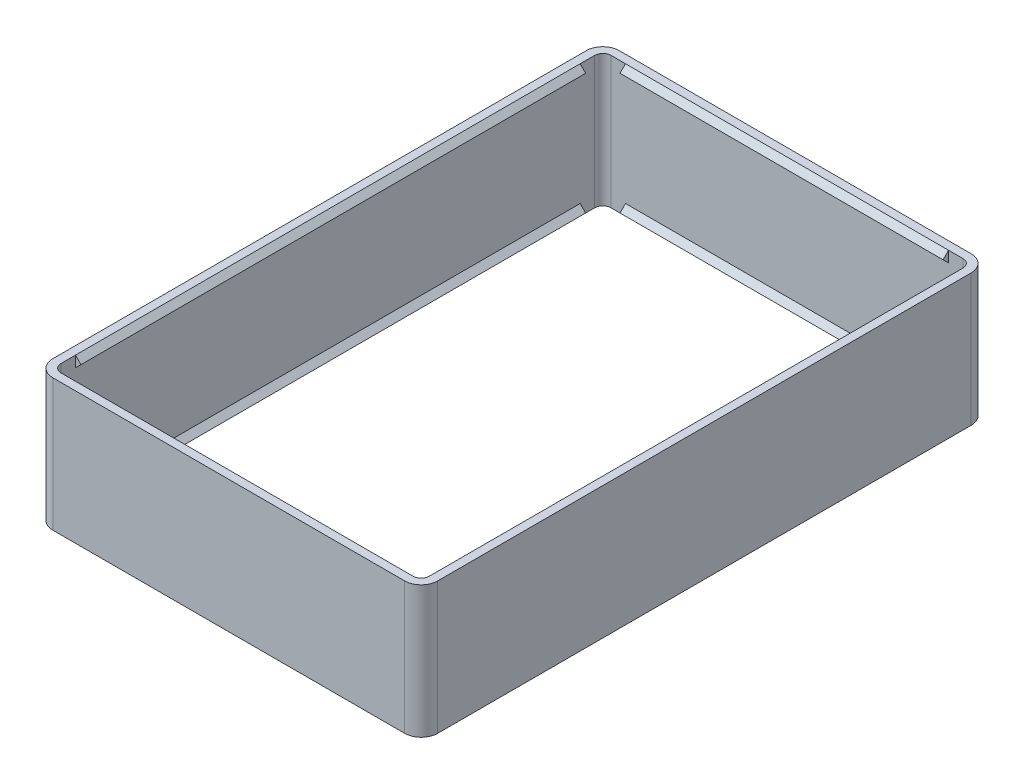
SolidWorks part; units mm, degrees
ref_plane "Front Plane" through (0, 0, 0) normal (0, 0, 1) x (1, 0, 0)
ref_plane "Top Plane" through (0, 0, 0) normal (0, 1, 0) x (1, 0, 0)
ref_plane "Right Plane" through (0, 0, 0) normal (1, 0, 0) x (0, 0, -1)
sketch "Sketch1" plane through (0, 0, 0) normal (0, 1, 0) x (1, 0, 0)
  line L1 (-30.48, -46.99) -> (30.48, -46.99) construction
  line L2 (-30.48, -46.99) -> (-30.48, 46.99) construction
  line L3 (-30.48, 46.99) -> (30.48, 46.99) construction
  line L4 (30.48, -46.99) -> (30.48, 46.99) construction
  line L5 (-30.48, -46.99) -> (30.48, 46.99) construction
  line L6 (-30.48, 46.99) -> (30.48, -46.99) construction
  line L7 (-34.98, -51.49) -> (34.98, -51.49)
  line L8 (-34.98, -51.49) -> (-34.98, 51.49)
  line L9 (-34.98, 51.49) -> (34.98, 51.49)
  line L10 (34.98, -51.49) -> (34.98, 51.49)
  line L11 (-34.98, -51.49) -> (34.98, 51.49) construction
  line L12 (-34.98, 51.49) -> (34.98, -51.49) construction
  line L13 (33.48, -49.99) -> (-33.48, -49.99)
  line L14 (33.48, -49.99) -> (33.48, 49.99)
  line L15 (33.48, 49.99) -> (-33.48, 49.99)
  line L16 (-33.48, -49.99) -> (-33.48, 49.99)
  line L17 (33.48, -49.99) -> (-33.48, 49.99) construction
  line L18 (33.48, 49.99) -> (-33.48, -49.99) construction
  point P0 (0, 0)
  point P6 (0, 0)
  point P11 (0, 0)
  dimension "D1" = 60.96
  dimension "D2" = 93.98
  dimension "D3" = 4.5
  dimension "D4" = 4.5
  dimension "D5" = 1.5
  dimension "D6" = 1.5
extrude "Boss-Extrude1" add sketch "Sketch1" along normal blind 24
fillet "Fillet1" radius 3 4 edges at (-34.98, 12, 51.49) (34.98, 12, 51.49) (34.98, 12, -51.49) (-34.98, 12, -51.49)
fillet "Fillet2" radius 1.5 4 edges at (-33.48, 12, 49.99) (-33.48, 12, -49.99) (33.48, 12, 49.99) (33.48, 12, -49.99)
ref_plane "Plane1" through (-29.3587, 0, 0) normal (1, 0, 0) x (0, 0, -1)
ref_plane "Plane2" through (0, 0, 45.8687) normal (0, 0, -1) x (-1, 0, 0)
ref_plane "Plane3" through (0, 0, -45.8687) normal (0, 0, 1) x (1, 0, 0)
ref_plane "Plane4" through (29.3587, 0, 0) normal (-1, 0, 0) x (0, 0, 1)
sketch "Sketch2" plane through (0, 0, 0) normal (1, 0, 0) x (0, 0, -1)
  line L0 (-49.99, 24) -> (-49.99, 22)
  line L1 (-48.49, 24) -> (-51.49, 24) construction
  line L2 (-49.99, 0) -> (-49.99, 24) construction
  line L3 (-49.99, 22) -> (-48.99, 23)
  line L4 (-48.99, 23) -> (-49.99, 24)
  line L5 (49.99, 24) -> (49.99, 22)
  line L6 (49.99, 24) -> (49.99, 0) construction
  line L7 (49.99, 22) -> (48.99, 23)
  line L8 (48.99, 23) -> (49.99, 24)
  line L9 (-49.99, 0) -> (-49.99, 2)
  line L10 (-51.49, 0) -> (-48.49, 0) construction
  line L11 (-49.99, 2) -> (-48.99, 1)
  line L12 (-48.99, 1) -> (-49.99, 0)
  line L13 (49.99, 0) -> (49.99, 2)
  line L14 (48.49, 0) -> (51.49, 0) construction
  line L15 (49.99, 2) -> (48.99, 1)
  line L16 (48.99, 1) -> (49.99, 0)
extrude "Boss-Extrude2" add sketch "Sketch2" along normal up to surface (29.3587 mm away) and the other way up to surface (29.3587 mm away) up to plane "Plane4" other way up to plane "Plane1"
sketch "Sketch3" plane through (0, 0, 0) normal (0, 0, 1) x (1, 0, 0)
  line L0 (-33.48, 24) -> (-33.48, 22)
  line L1 (-31.98, 24) -> (-34.98, 24) construction
  line L2 (-33.48, 0) -> (-33.48, 24) construction
  line L3 (-33.48, 22) -> (-32.48, 23)
  line L4 (-32.48, 23) -> (-33.48, 24)
  line L5 (-33.48, 0) -> (-33.48, 2)
  line L6 (-33.48, 2) -> (-32.48, 1)
  line L7 (-32.48, 1) -> (-33.48, 0)
  line L8 (33.48, 24) -> (33.48, 22)
  line L9 (33.48, 24) -> (33.48, 0) construction
  line L10 (33.48, 22) -> (32.48, 23)
  line L11 (32.48, 23) -> (33.48, 24)
  line L12 (33.48, 0) -> (33.48, 2)
  line L13 (33.48, 2) -> (32.48, 1)
  line L14 (32.48, 1) -> (33.48, 0)
extrude "Boss-Extrude3" add sketch "Sketch3" against normal up to surface (45.8687 mm away) and the other way up to surface (45.8687 mm away) up to plane "Plane3" other way up to plane "Plane2"
equation "\"D1@Sketch1\"=\"WIDTH\""
equation "\"D2@Sketch1\"= \"LENGTH\""
equation "\"D1@Boss-Extrude1\"=\"HEIGHT\""
equation "\"LENGTH\"= 3.7in  'longest of two dimensions of pcb"
equation "\"WIDTH\"= 2.4in   'shortest of two dimensions of pcb"
equation "\"HOLE_DIA\"= 0.1in  'mounting hole diameter"
equation "\"HOLE_DIST\"= 0.137795in  'distance to mount hole centerline from edge of PCB"
equation "\"HEIGHT\"= 0.944882in  'height of the enclosure"
